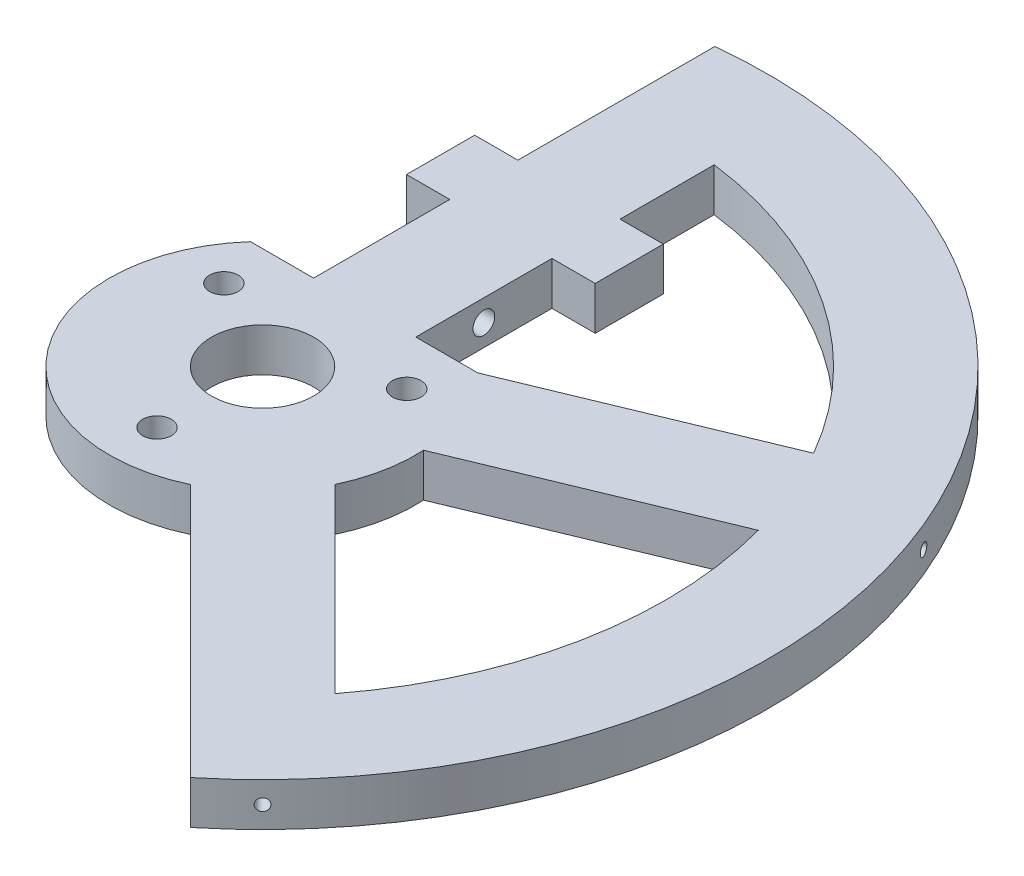
SolidWorks part; units mm, degrees
material "6061 Alloy"
ref_plane "Front Plane" through (0, 0, 0) normal (0, 0, 1) x (1, 0, 0)
ref_plane "Top Plane" through (0, 0, 0) normal (0, 1, 0) x (1, 0, 0)
ref_plane "Right Plane" through (0, 0, 0) normal (1, 0, 0) x (0, 0, -1)
sketch "Sketch1" plane through (0, 0, 0) normal (0, 1, 0) x (1, 0, 0)
  line L0 (0, 0) -> (0, 74.3) construction
  line L1 (0, 0) -> (52.538, -52.538) construction
  line L2 (20.3033, -9.6967) -> (46.898, -36.2914)
  line L3 (7.5, 15) -> (7.5, 35)
  line L4 (-7.5, -3.1066) -> (-5.3033, -5.3033) construction
  line L5 (-7.5, 21.2132) -> (-7.5, 14.1697) construction
  line L6 (-7.5, -3.1066) -> (-7.5, 74.3) construction
  line L7 (7.5, 3.1066) -> (7.5, 74.3) construction
  line L8 (-7.5, -3.1066) -> (47.2347, -57.8413) construction
  line L9 (7.5, 3.1066) -> (57.8413, -47.2347) construction
  line L10 (46.898, -36.2914) -> (57.573, -46.9664) construction
  line L11 (7.5, 58.8238) -> (7.5, 73.9205) construction
  line L12 (0, 0) -> (68.6442, 28.4334) construction
  line L13 (22.4686, 1.1888) -> (57.2162, 15.5818)
  line L14 (-2.8701, 6.9291) -> (0, 8.1179) construction
  line L15 (2.8701, -6.9291) -> (5.7403, -5.7403) construction
  line L16 (2.8701, -6.9291) -> (71.5144, 21.5043) construction
  line L17 (5.7403, -5.7403) -> (13.2403, -2.6336) construction
  line L18 (7.5, 3.1066) -> (13.2403, -2.6336) construction
  line L19 (7.5, 3.1066) -> (7.5, 11.2245) construction
  line L20 (0, 8.1179) -> (7.5, 11.2245) construction
  line L21 (7.5, 11.2245) -> (9.0849, 11.881) construction
  line L22 (-2.8701, 6.9291) -> (65.7741, 35.3625) construction
  line L23 (51.476, 29.44) -> (65.4235, 35.2172) construction
  line L24 (65.4235, 35.2172) -> (65.7741, 35.3625)
  line L25 (57.2162, 15.5818) -> (71.1638, 21.3591) construction
  line L26 (71.1638, 21.3591) -> (71.5144, 21.5043)
  line L27 (13.2403, -2.6336) -> (20.3033, -9.6967) construction
  line L28 (13.85, 5) -> (7.5, 5) construction
  line L29 (13.85, 17.7321) -> (13.85, 15) construction
  line L30 (13.85, 45) -> (7.5, 45)
  line L31 (-13.85, 17.7321) -> (-13.85, 15) construction
  line L32 (13.85, 5) -> (-13.85, 45) construction
  line L33 (13.85, 45) -> (-13.85, 5) construction
  line L34 (-13.85, 35) -> (-7.5, 35)
  line L35 (-13.85, 35) -> (-13.85, 15) construction
  line L36 (-16.7705, 15) -> (-7.5, 15)
  line L37 (-7.5, 35) -> (-7.5, 15)
  line L38 (7.5, 15) -> (16.6148, 15)
  line L39 (7.5, 15) -> (7.5, 35)
  line L40 (7.5, 35) -> (13.85, 35)
  line L41 (13.85, 15) -> (13.85, 35) construction
  line L42 (13.2403, -2.6336) -> (22.4686, 1.1888) construction
  line L43 (7.5, 5) -> (-7.5274, 5) construction
  line L44 (-7.5, 5) -> (-13.85, 5) construction
  line L45 (-7.5274, 5) -> (0, 5) construction
  line L46 (0, 5) -> (-7.5, 5) construction
  line L47 (13.85, 5) -> (13.85, 13.8548) construction
  line L48 (16.6148, 15) -> (16.7283, 15.047)
  line L49 (16.7283, 15.047) -> (51.476, 29.44)
  line L50 (13.85, 13.8548) -> (13.85, 17.7321) construction
  line L51 (9.0849, 11.881) -> (13.85, 13.8548) construction
  line L52 (7.5, 11.2245) -> (7.5, 21.2132) construction
  line L53 (7.5, 21.2132) -> (7.5, 14.1697) construction
  line L54 (-5.3033, -5.3033) -> (9.6967, -20.3033) construction
  line L55 (9.6967, -20.3033) -> (46.9664, -57.573)
  line L56 (-7.5, -3.1066) -> (-7.5, 0) construction
  line L57 (-7.5, 0) -> (-7.5, 5) construction
  line L58 (-13.85, 5) -> (-13.85, 17.7321) construction
  line L59 (-7.5, 5) -> (-7.5, 21.2132) construction
  line L60 (-7.5, 14.1697) -> (-7.5, 15) construction
  line L61 (-7.5, 15) -> (-7.5, 35) construction
  line L62 (-13.85, 15) -> (-13.85, 35) construction
  line L63 (-13.85, 35) -> (-13.85, 45)
  line L64 (13.85, 15) -> (13.85, 35) construction
  line L65 (13.85, 35) -> (13.85, 45)
  line L66 (0, 45) -> (-7.5, 45) construction
  line L67 (-7.5, 45) -> (-13.85, 45)
  line L68 (7.5, 45) -> (0, 45) construction
  line L69 (7.5, 14.1697) -> (7.5, 15) construction
  line L70 (7.5, 35.8303) -> (7.5, 45) construction
  line L71 (7.5, 45) -> (7.5, 58.8238)
  line L72 (7.5, 35) -> (7.5, 35.8303) construction
  line L73 (-7.5, 35) -> (-7.5, 35.8303) construction
  line L74 (-7.5, 45) -> (-7.5, 73.9205)
  line L75 (-7.5, 35.8303) -> (-7.5, 45) construction
  line L77 (13.85, 13.8548) -> (16.6148, 15) construction
  arc A0 (46.9664, -57.573) -> (-7.5, 73.9205) centre (0, 0) ccw
  arc A1 (46.898, -36.2914) -> (57.2162, 15.5818) centre (0, 0) ccw
  arc A2 (-7.5, 73.9205) -> (46.9664, -57.573) centre (0, 0) ccw construction
  circle A3 centre (0, 0) radius 74.3 construction
  arc A4 (41.9314, -41.9314) -> (46.898, -36.2914) centre (0, 0) ccw construction
  circle A5 centre (0, 0) radius 59.3 construction
  arc A6 (36.2914, -46.898) -> (41.9314, -41.9314) centre (0, 0) ccw construction
  arc A7 (-7.5, 58.8238) -> (36.2914, -46.898) centre (0, 0) ccw construction
  arc A8 (7.5, 58.8238) -> (0, 59.3) centre (0, 0) ccw construction
  arc A9 (0, 59.3) -> (-7.5, 58.8238) centre (0, 0) ccw construction
  arc A10 (57.2162, 15.5818) -> (54.7861, 22.6931) centre (0, 0) ccw construction
  arc A11 (51.476, 29.44) -> (7.5, 58.8238) centre (0, 0) ccw
  arc A12 (54.7861, 22.6931) -> (51.476, 29.44) centre (0, 0) ccw construction
  arc A13 (20.3033, -9.6967) -> (22.4686, 1.1888) centre (0, 0) ccw
  circle A14 centre (0, 0) radius 7.5
  arc A15 (9.6967, -20.3033) -> (15.9099, -15.9099) centre (0, 0) ccw construction
  arc A16 (15.9099, -15.9099) -> (20.3033, -9.6967) centre (0, 0) ccw construction
  arc A17 (22.4686, 1.1888) -> (20.7873, 8.6104) centre (0, 0) ccw construction
  arc A18 (16.7283, 15.047) -> (13.85, 17.7321) centre (0, 0) ccw construction
  arc A19 (20.7873, 8.6104) -> (16.7283, 15.047) centre (0, 0) ccw construction
  arc A20 (13.85, 17.7321) -> (1.7801, 22.4295) centre (0, 0) ccw construction
  arc A21 (-7.5, 21.2132) -> (-13.85, 17.7321) centre (0, 0) ccw construction
  arc A22 (1.7801, 22.4295) -> (-13.85, 17.7321) centre (0, 0) ccw construction
  arc A23 (7.5, 21.2132) -> (0, 22.5) centre (0, 0) ccw construction
  arc A24 (0, 22.5) -> (-7.5, 21.2132) centre (0, 0) ccw construction
  arc A25 (-1.7801, 22.4295) -> (-13.85, 17.7321) centre (0, 0) ccw construction
  arc A26 (-16.7705, 15) -> (9.6967, -20.3033) centre (0, 0) ccw
  arc A27 (-13.85, 17.7321) -> (-16.7705, 15) centre (0, 0) ccw construction
  arc A28 (-16.7705, 15) -> (-1.7801, 22.4295) centre (0, 0) ccw construction
  arc A29 (-13.85, 17.7321) -> (-16.7705, 15) centre (0, 0) ccw construction
  arc A30 (-13.85, 17.7321) -> (-16.7705, 15) centre (0, 0) ccw construction
  arc A31 (-16.7705, 15) -> (7.5, 21.2132) centre (0, 0) ccw construction
  point P77 (0, 25)
  dimension "D1" = 148.6
  dimension "D11" = 45
  dimension "D12" = 15
  dimension "D2" = 135
  dimension "D6" = 67.5
  dimension "D9" = 27.7
  dimension "D10" = 40
  dimension "D13" = 5
  dimension "D14" = 10
  dimension "D15" = 10
  dimension "D3" = 7.5
  dimension "D4" = 7.5
  dimension "D5" = 15
  dimension "D7" = 7.5
  dimension "D8" = 7.5
extrude "Boss-Extrude1" add sketch "Sketch1" along normal mid plane 6.35 contours L31 A26 L55 A0 L74 L67 L63 L34 L37 L36 L49 A18 L29 L38 L3 L40 L65 L30 L71 A11 L2 A13 L13 A1 A14 region at (27.267, 0, -11.9761)
hole_wizard "M5x0.8 Tapped Hole2" positions "Sketch2" profile "Sketch3" tap size "M5x0.8" standard "ANSI Metric" end condition through all
sketch "Sketch2" plane through (0, 3.175, 0) normal (0, 1, 0) x (1, 0, 0)
  line L1 (0, 0) -> (-13.4234, 7.75) construction
  line L3 (13.4234, 7.75) -> (0, 0) construction
  line L4 (0, 0) -> (0, -15.5) construction
  circle A0 centre (0, 0) radius 15.5 construction
  point P10 (-13.4234, 7.75)
  point P12 (13.4234, 7.75)
  point P16 (0, -15.5)
  dimension "D1" = 31
  dimension "D2" = 120
  dimension "D3" = 120
sketch "Sketch3" plane through (0, 3.175, 15.5) normal (1, 0, 0) x (0, 0, 1)
  line L0 (0, 0) -> (0, 6.35)
  line L1 (0, 6.35) -> (2.1, 6.35)
  line L2 (2.1, 6.35) -> (2.1, 0)
  line L5 (2.1, 0) -> (0, 0)
  line L11 (0, -6.35) -> (0, 107.95) construction
  dimension "Thru Tap Drill Dia." = 4.2
  dimension "Thru Tap Drill Depth" = 6.35
ref_plane "Plane1" through (0, 0, -74.3) normal (0, 0, -1) x (-1, 0, 0)
hole_wizard "M2.2x0.45 Tapped Hole1" positions "Sketch4" profile "Sketch5" tap size "M2.2x0.45" standard "ANSI Metric"
sketch "Sketch4" plane through (0, 0, -74.3) normal (0, 0, -1) x (-1, 0, 0)
  point P0 (0, 0)
sketch "Sketch5" plane through (0, 0, -74.3) normal (1, 0, 0) x (0, 1, 0)
  line L0 (0, 0) -> (0, 10.5258)
  line L1 (0, 10.5258) -> (0.875, 10)
  line L2 (0.875, 10) -> (0.875, 0)
  line L5 (0.875, 0) -> (0, 0)
  line L10 (0, 10.5258) -> (-0.875, 10) construction
  line L11 (0, -6.35) -> (0, 107.95) construction
  dimension "Tap Drill Dia." = 1.75
  dimension "Tap Drill Depth" = 10
  dimension "Drill Angle" = 118
pattern_circular "CirPattern1" count 3 over 135 about axis through (0, 3.175, 0) along (0, -1, 0) of "M2.2x0.45 Tapped Hole1"
hole_wizard "M3 Clearance Hole1" positions "Sketch6" profile "Sketch7" hole size "M3" standard "ANSI Metric" end condition up to next
sketch "Sketch6" plane through (-7.5, 0, 0) normal (-1, 0, 0) x (0, 0, 1)
  line L1 (-35, 3.175) -> (-15, 3.175)
  line L2 (-35, 3.175) -> (-35, -3.175)
  line L3 (-35, -3.175) -> (-15, -3.175)
  line L4 (-15, 3.175) -> (-15, -3.175)
  line L5 (-35, 3.175) -> (-15, -3.175) construction
  line L6 (-35, -3.175) -> (-15, 3.175) construction
  point P199 (-25, 0)
sketch "Sketch7" plane through (-7.5, 0, -25) normal (0, 1, 0) x (0, 0, 1)
  line L0 (0, 0) -> (0, 15)
  line L1 (0, 15) -> (1.6, 15)
  line L2 (1.6, 15) -> (1.6, 0)
  line L5 (1.6, 0) -> (0, 0)
  line L11 (0, -6.35) -> (0, 107.95) construction
  dimension "Thru Hole Dia." = 3.2
  dimension "Thru Hole Depth" = 15
